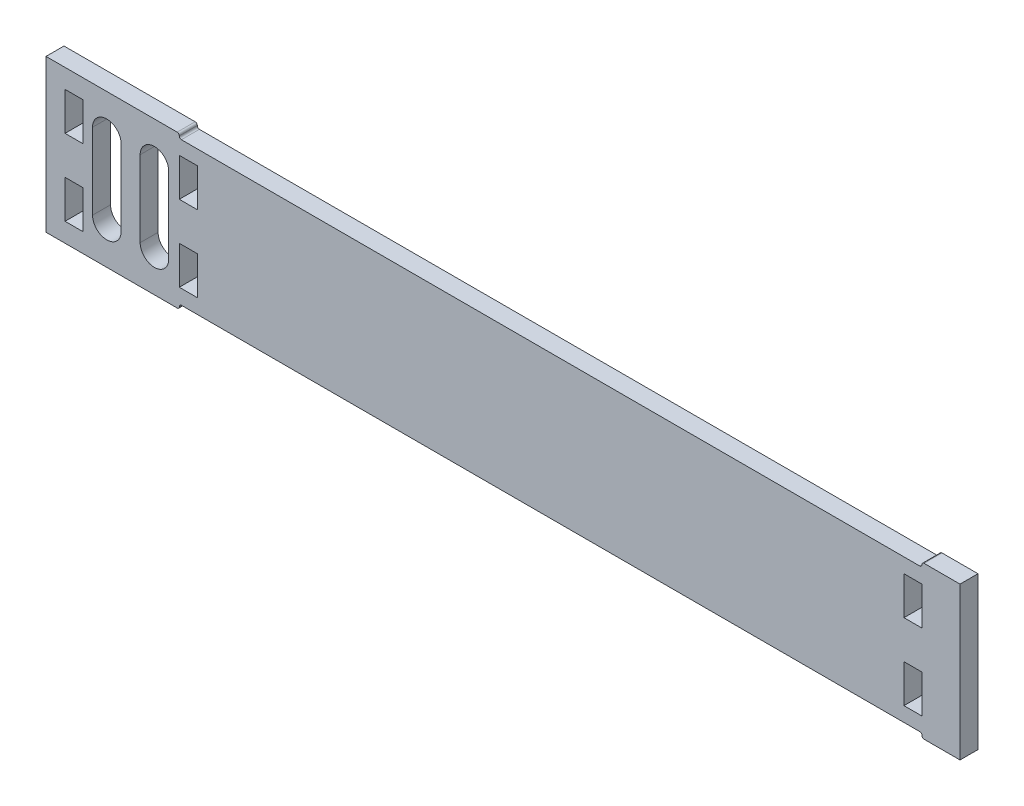
SolidWorks part; units mm, degrees
ref_plane "Front Plane" through (0, 0, 0) normal (0, 0, 1) x (1, 0, 0)
ref_plane "Top Plane" through (0, 0, 0) normal (0, 1, 0) x (1, 0, 0)
ref_plane "Right Plane" through (0, 0, 0) normal (1, 0, 0) x (0, 0, -1)
sketch "Sketch1" plane through (0, 0, 0) normal (0, 0, 1) x (1, 0, 0)
  line L0 (-18.6944, 19.05) -> (-18.6944, 6.35)
  line L1 (0, 0) -> (-304.8, 0)
  line L2 (0, 0) -> (0, 50.8)
  line L3 (0, 50.8) -> (-304.8, 50.8)
  line L4 (-304.8, 0) -> (-304.8, 50.8)
  line L5 (-18.6944, 44.45) -> (-12.7, 44.45)
  line L6 (-18.6944, 44.45) -> (-18.6944, 31.75)
  line L7 (-18.6944, 31.75) -> (-12.7, 31.75)
  line L8 (-12.7, 44.45) -> (-12.7, 31.75)
  line L9 (-18.6944, 19.05) -> (-12.7, 19.05)
  line L10 (-12.7, 19.05) -> (-12.7, 6.35)
  line L11 (-18.6944, 6.35) -> (-12.7, 6.35)
  line L12 (-260.35, 31.75) -> (-254.3556, 31.75)
  line L13 (-260.35, 44.45) -> (-260.35, 31.75)
  line L14 (-260.35, 44.45) -> (-254.3556, 44.45)
  line L15 (-254.3556, 44.45) -> (-254.3556, 31.75)
  line L16 (-260.35, 19.05) -> (-254.3556, 19.05)
  line L17 (-260.35, 19.05) -> (-260.35, 6.35)
  line L18 (-260.35, 6.35) -> (-254.3556, 6.35)
  line L19 (-254.3556, 19.05) -> (-254.3556, 6.35)
  line L20 (-292.4556, 19.05) -> (-292.4556, 6.35)
  line L21 (-298.45, 6.35) -> (-292.4556, 6.35)
  line L22 (-298.45, 19.05) -> (-298.45, 6.35)
  line L23 (-298.45, 19.05) -> (-292.4556, 19.05)
  line L24 (-298.45, 31.75) -> (-292.4556, 31.75)
  line L25 (-298.45, 44.45) -> (-298.45, 31.75)
  line L26 (-298.45, 44.45) -> (-292.4556, 44.45)
  line L27 (-292.4556, 44.45) -> (-292.4556, 31.75)
  dimension "D1" = 50.8
  dimension "D2" = 304.8
  dimension "D3" = 5.9944
  dimension "D4" = 12.7
  dimension "D5" = 6.35
  dimension "D7" = 12.7
  dimension "D9" = 44.45
  dimension "D6" = 2
  dimension "D8" = 2
  dimension "D10" = 2
extrude "Boss-Extrude1" add sketch "Sketch1" along normal blind 5.9944
sketch "Sketch2" plane through (0, 0, 5.9944) normal (0, 0, 1) x (1, 0, 0)
  line L0 (-284.5181, 12.7) -> (-284.5181, 38.1) construction
  line L1 (-289.2806, 12.7) -> (-289.2806, 38.1)
  line L2 (-279.7556, 12.7) -> (-279.7556, 38.1)
  line L3 (-292.4556, 6.35) -> (-292.4556, 19.05) construction
  line L4 (-304.8, 25.4) -> (-254.6177, 25.4) construction
  line L5 (-304.8, 50.8) -> (-304.8, 0) construction
  line L6 (-288.925, 25.4) -> (-238.7427, 25.4) construction
  line L7 (-268.6431, 12.7) -> (-268.6431, 38.1) construction
  line L8 (-273.4056, 12.7) -> (-273.4056, 38.1)
  line L9 (-284.5181, 44.45) -> (-284.5181, 6.35) construction
  line L10 (-268.5161, 44.45) -> (-268.5161, 6.35) construction
  line L11 (-263.8806, 12.7) -> (-263.8806, 38.1)
  arc A0 (-289.2806, 12.7) -> (-279.7556, 12.7) centre (-284.5181, 12.7) ccw
  arc A1 (-279.7556, 38.1) -> (-289.2806, 38.1) centre (-284.5181, 38.1) ccw
  arc A2 (-273.4056, 12.7) -> (-263.8806, 12.7) centre (-268.6431, 12.7) ccw
  arc A3 (-263.8806, 38.1) -> (-273.4056, 38.1) centre (-268.6431, 38.1) ccw
  point P2 (-284.5181, 25.4)
  point P20 (-268.6431, 25.4)
  dimension "D2" = 4.7625
  dimension "D1" = 25.4
  dimension "D3" = 7.9375
  dimension "D5" = 15.875
  dimension "D4" = 2
extrude "Cut-Extrude2" cut sketch "Sketch2" against normal blind 5.9944
sketch "Sketch3" plane through (0, 0, 5.9944) normal (0, 0, 1) x (1, 0, 0)
  line L0 (0, 50.8) -> (-304.8, 50.8) construction
  line L1 (-260.35, 50.8) -> (-12.7, 50.8)
  line L2 (-260.35, 50.8) -> (-260.35, 49.3125)
  line L3 (-260.35, 49.3125) -> (-12.7, 49.3125)
  line L4 (-12.7, 50.8) -> (-12.7, 49.3125)
  line L7 (-260.35, 44.45) -> (-260.35, 31.75) construction
  line L8 (-12.7, 31.75) -> (-12.7, 44.45) construction
  line L9 (-304.8, 25.4) -> (0, 25.4) construction
  line L10 (-304.8, 50.8) -> (-304.8, 0) construction
  line L11 (0, 0) -> (0, 50.8) construction
  line L12 (-12.7, 0) -> (-12.7, 1.4875)
  line L13 (-260.35, 1.4875) -> (-12.7, 1.4875)
  line L14 (-260.35, 0) -> (-260.35, 1.4875)
  line L15 (-260.35, 0) -> (-12.7, 0)
  dimension "D1" = 1.4875
extrude "Cut-Extrude3" cut sketch "Sketch3" against normal through all
fillet "Fillet4" radius 0.7 8 edges at (-12.7, 50.8, 2.9972) (-12.7, 49.3125, 2.9972) (-260.35, 50.8, 2.9972) (-260.35, 49.3125, 2.9972) (-260.35, 0, 2.9972) (-260.35, 1.4875, 2.9972) (-12.7, 0, 2.9972) (-12.7, 1.4875, 2.9972)
